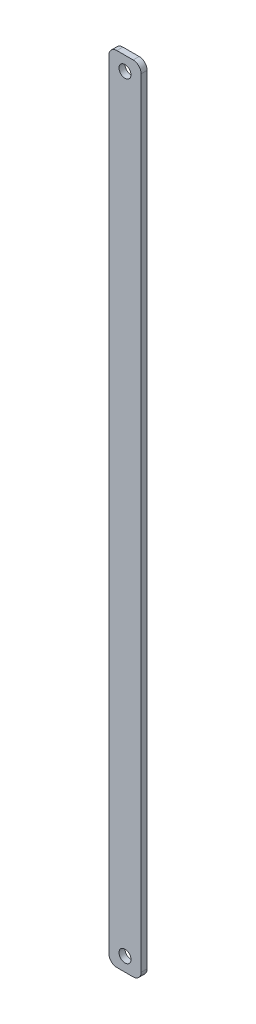
SolidWorks part; units mm, degrees
ref_plane "Front Plane" through (0, 0, 0) normal (0, 0, 1) x (1, 0, 0)
ref_plane "Top Plane" through (0, 0, 0) normal (0, 1, 0) x (1, 0, 0)
ref_plane "Right Plane" through (0, 0, 0) normal (1, 0, 0) x (0, 0, -1)
sketch "Sketch1" plane through (0, 0, 0) normal (0, 1, 0) x (1, 0, 0)
  line L1 (-4.03, -0.75) -> (4.03, -0.75)
  line L2 (-4.03, -0.75) -> (-4.03, 0.75)
  line L3 (-4.03, 0.75) -> (4.03, 0.75)
  line L4 (4.03, -0.75) -> (4.03, 0.75)
  line L5 (-4.03, -0.75) -> (4.03, 0.75) construction
  line L6 (-4.03, 0.75) -> (4.03, -0.75) construction
  point P0 (0, 0)
  dimension "D1" = 8.06
  dimension "D2" = 1.5
extrude "Boss-Extrude1" add sketch "Sketch1" along normal blind 198.5
sketch "Sketch2" plane through (0, 0, 0.75) normal (0, 0, 1) x (1, 0, 0)
  line L0 (-4.03, 198.5) -> (-4.03, 0) construction
  line L1 (-4.03, 198.5) -> (4.03, 198.5) construction
  line L3 (4.03, 198.5) -> (4.03, 0) construction
  circle A0 centre (0, 3.5) radius 1.5
  circle A1 centre (0, 195) radius 1.5
  point P5 (0, 0)
  dimension "D2" = 3
  dimension "D4" = 3
  dimension "D1" = 3.5
  dimension "D3" = 4.03
  dimension "D5" = 3.5
  dimension "D6" = 4.03
extrude "Cut-Extrude1" cut sketch "Sketch2" against normal up to surface (1.5 mm away) up to face at (0, 99.25, -0.75)
fillet "Fillet1" radius 2 4 edges at (-4.03, 0, 0) (4.03, 0, 0) (-4.03, 198.5, 0) (4.03, 198.5, 0)
